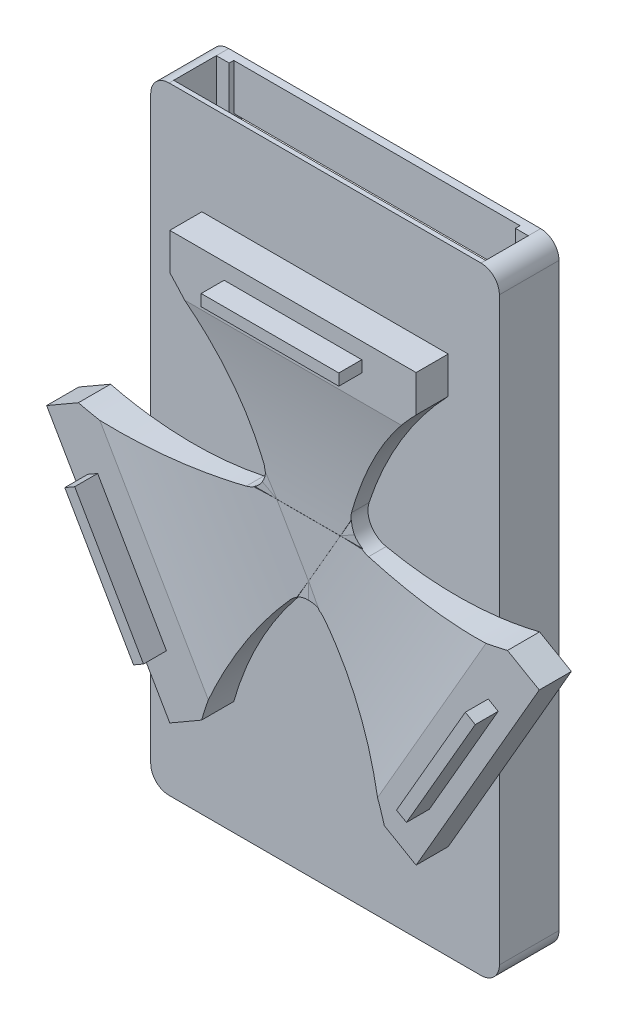
SolidWorks part; units mm, degrees
ref_plane "Plano frontal" through (0, 0, 0) normal (0, 0, 1) x (1, 0, 0)
ref_plane "Plano superior" through (0, 0, 0) normal (0, 1, 0) x (1, 0, 0)
ref_plane "Plano direito" through (0, 0, 0) normal (1, 0, 0) x (0, 0, -1)
sketch "Esboço1" plane through (0, 0, 0) normal (0, 0, 1) x (1, 0, 0)
  line L16 (-26.8468, 46.5) -> (26.8468, 46.5)
  line L31 (-26.8468, -46.5) -> (-53.6936, 0)
  line L36 (53.6936, 0) -> (26.8468, -46.5)
  line L38 (26.8468, 46.5) -> (26.8468, 38.5)
  line L39 (-26.8468, 38.5) -> (-26.8468, 46.5)
  line L40 (-53.6936, 0) -> (-46.7654, 4)
  line L41 (-26.8468, -46.5) -> (-19.9186, -42.5)
  line L42 (26.8468, -46.5) -> (19.9186, -42.5)
  line L43 (46.7654, 4) -> (53.6936, 0)
  arc A10 (-26.8468, 38.5) -> (-9.603, 9.8434) centre (-80.7333, -13.442) cw
  arc A12 (26.8468, 38.5) -> (9.603, 9.8434) centre (80.7333, -13.442) ccw
  arc A13 (-19.9186, -42.5) -> (-3.7231, -13.2381) centre (52.0077, -63.1961) cw
  arc A14 (-46.7654, 4) -> (-13.3261, 3.3948) centre (-28.7255, 76.6381) ccw
  arc A18 (19.9186, -42.5) -> (3.7231, -13.2381) centre (-52.0077, -63.1961) ccw
  arc A20 (46.7654, 4) -> (13.3261, 3.3948) centre (28.7255, 76.6381) cw
  arc A25 (-9.603, 9.8434) -> (-13.3261, 3.3948) centre (-14.3549, 8.2878) cw
  arc A26 (13.3261, 3.3948) -> (9.603, 9.8434) centre (14.3549, 8.2878) cw
  arc A27 (3.7231, -13.2381) -> (-3.7231, -13.2381) centre (0, -16.5756) ccw
  dimension "D1" = 5
  dimension "D2" = 5
  dimension "D3" = 5
extrude "Ressalto-extrusão1" add sketch "Esboço1" along normal blind 7
sketch "Esboço2" plane through (0, 0, 7) normal (0, 0, 1) x (1, 0, 0)
  line L0 (37.2391, -21.5) -> (44.7391, -8.5096)
  line L1 (42.574, -7.2596) -> (27.574, -33.2404)
  line L2 (0, 43) -> (-15, 43)
  line L3 (37.2391, -21.5) -> (29.7391, -34.4904)
  line L4 (-15, 40.5) -> (15, 40.5)
  line L5 (0, 43) -> (15, 43)
  line L6 (44.7391, -8.5096) -> (42.574, -7.2596)
  line L9 (-15, 43) -> (-15, 40.5)
  line L10 (15, 43) -> (15, 40.5)
  line L12 (29.7391, -34.4904) -> (27.574, -33.2404)
  line L14 (-37.2391, -21.5) -> (-29.7391, -34.4904)
  line L15 (-27.574, -33.2404) -> (-42.574, -7.2596)
  line L16 (-37.2391, -21.5) -> (-44.7391, -8.5096)
  line L17 (-29.7391, -34.4904) -> (-27.574, -33.2404)
  line L18 (-44.7391, -8.5096) -> (-42.574, -7.2596)
extrude "Ressalto-extrusão2" add sketch "Esboço2" along normal blind 5
sketch "Esboço3" plane through (0, 0, 0) normal (0, 0, -1) x (-1, 0, 0)
  line L0 (38, 63.2507) -> (38, -63.2507)
  line L1 (-34, -67.2507) -> (34, -67.2507)
  line L2 (-34, 67.2507) -> (34, 67.2507)
  line L3 (-38, 63.2507) -> (-38, -63.2507)
  arc A0 (38, 63.2507) -> (34, 67.2507) centre (34, 63.2507) ccw
  arc A1 (-34, 67.2507) -> (-38, 63.2507) centre (-34, 63.2507) ccw
  arc A2 (-38, -63.2507) -> (-34, -67.2507) centre (-34, -63.2507) ccw
  arc A3 (34, -67.2507) -> (38, -63.2507) centre (34, -63.2507) ccw
extrude "Ressalto-extrusão3" add sketch "Esboço3" along normal blind 13
sketch "Esboço4" plane through (0, 67.2507, 0) normal (0, 1, 0) x (1, 0, 0)
  line L0 (34.2, 1) -> (-34.2, 1)
  line L1 (0, 1) -> (0, 0)
  line L2 (34.2, 1) -> (34.2, 10.3)
  line L3 (-34.2, 1) -> (-34.2, 10.3)
  line L4 (-31.2, 10.3) -> (-34.2, 10.3)
  line L5 (31.2, 10.3) -> (34.2, 10.3)
  line L7 (31.2, 10.3) -> (31.2, 11.3)
  line L8 (-31.2, 10.3) -> (-31.2, 11.3)
  line L11 (-31.2, 11.3) -> (31.2, 11.3)
  line M10 (34, 0) -> (34, 13)
  line M11 (34, 13) -> (-34, 13)
  line M12 (-34, 13) -> (-34, 0)
extrude "Corte-extrusão1" cut sketch "Esboço4" against normal blind 131 contours L8 L4 L0 L5 L7 M12 M10 M11 | L8 L7 M11 region at (0, 67.2507, -6.1125)
sketch "Esboço6" plane through (-26.8468, 0, 0) normal (-1, 0, 0) x (0, 0, 1)
  line L2 (18.5163, 34.9447) -> (7, 34.9447)
  line L3 (3.5763, 4) -> (21.2226, 4)
  line L6 (21.2226, 4) -> (18.5163, 34.9447)
  arc A0 (7, 34.9447) -> (3.5763, 4) centre (196.4927, -1.6822) ccw
extrude "Corte-extrusão2" cut sketch "Esboço6" against normal blind 60
sketch "Esboço8" plane through (13.4234, -23.25, 0) normal (0.5, -0.866, 0) x (0.866, 0.5, 0)
  line L2 (-34.9447, 18.5163) -> (-34.9447, 7)
  line L3 (-4, 3.5763) -> (-4, 21.2226)
  line L4 (-4, 21.2226) -> (-34.9447, 18.5163)
  arc A0 (-34.9447, 7) -> (-4, 3.5763) centre (1.6822, 196.4927) ccw
extrude "Corte-extrusão3" cut sketch "Esboço8" against normal blind 58
sketch "Esboço10" plane through (13.4234, 23.25, 0) normal (0.5, 0.866, 0) x (0.866, -0.5, 0)
  line L2 (34.9447, -18.5163) -> (34.9447, -7)
  line L3 (4, -3.5763) -> (4, -21.2226)
  line L4 (4, -21.2226) -> (34.9447, -18.5163)
  arc A0 (34.9447, -7) -> (4, -3.5763) centre (-1.6822, -196.4927) ccw
extrude "Corte-extrusão4" cut sketch "Esboço10" against normal blind 53
sketch "Esboço11" plane through (0, 0, 7) normal (0, 0, 1) x (1, 0, 0)
  line L0 (-6.9282, 4) -> (6.9282, 4)
  line L1 (6.9282, 4) -> (0, -8)
  line L2 (0, -8) -> (-6.9282, 4)
extrude "Corte-extrusão5" cut sketch "Esboço11" against normal blind 3.4
sketch "Esboço12" plane through (0, 67.2507, 0) normal (0, 1, 0) x (1, 0, 0)
  line L0 (-31.2, 11.3) -> (-31.2, 13)
  line L1 (-34, 13) -> (34, 13) construction
  line L2 (31.2, 11.3) -> (31.2, 13)
sketch "Esboço13" plane through (0, 0, -13) normal (0, 0, -1) x (-1, 0, 0)
  line L0 (-31.2, 57.2507) -> (-31.2, 5)
  line L1 (31.2, 57.2507) -> (31.2, 5)
  line L2 (-31.2, -63.7493) -> (31.2, -63.7493)
  line L6 (-31.2, 57.2507) -> (31.2, 57.2507)
  line L17 (-31.2, 5) -> (31.2, 5)
  line L18 (-31.2, -5) -> (-31.2, -63.7493)
  line L19 (31.2, -5) -> (31.2, -63.7493)
  line L20 (-31.2, -5) -> (31.2, -5)
extrude "Corte-extrusão6" cut sketch "Esboço13" against normal blind 3.4
